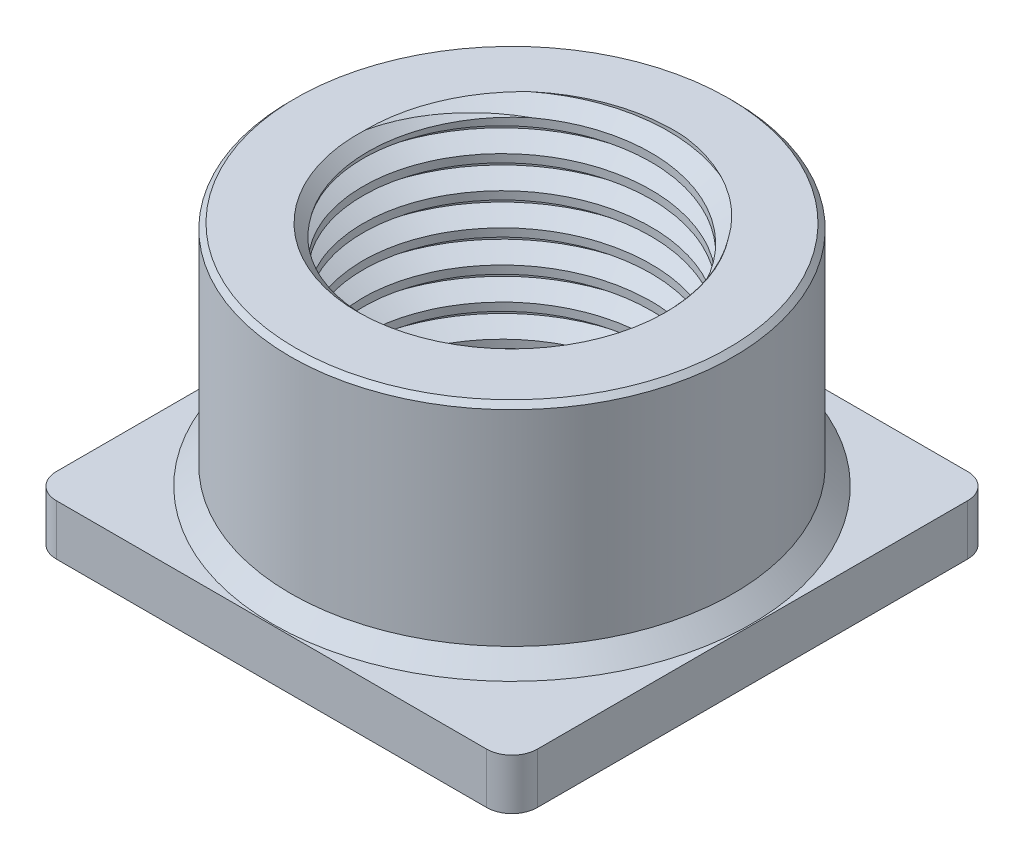
SolidWorks part; units mm, degrees
ref_plane "Front Plane" through (0, 0, 0) normal (0, 0, 1) x (1, 0, 0)
ref_plane "Top Plane" through (0, 0, 0) normal (0, 1, 0) x (1, 0, 0)
ref_plane "Right Plane" through (0, 0, 0) normal (1, 0, 0) x (0, 0, -1)
sketch "Sketch4" plane through (0, 0, 0) normal (0, 1, 0) x (1, 0, 0)
  circle A0 centre (0, 0) radius 5.69
  circle A1 centre (0, 0) radius 8.75
  dimension "D1" = 11.38
  dimension "D2" = 17.5
extrude "Boss-Extrude1" add sketch "Sketch4" along normal blind 9 separate body
sketch "Sketch7" plane through (0, 0, 0) normal (0, -1, 0) x (1, 0, 0)
  line L0 (-9.5, 9.5) -> (9.5, -9.5) construction
  line L1 (9.5, 9.5) -> (-9.5, 9.5)
  line L2 (9.5, 9.5) -> (9.5, -9.5)
  line L3 (9.5, -9.5) -> (-9.5, -9.5)
  line L4 (-9.5, 9.5) -> (-9.5, -9.5)
  circle A0 centre (0, 0) radius 6.75
  circle A1 centre (0, 0) radius 8.75 construction
  circle A2 centre (0, 0) radius 8.75 construction
  dimension "D2" = 2
  dimension "D1" = 19
extrude "Boss-Extrude2" add sketch "Sketch7" along normal blind 2
chamfer "Chamfer5" distance 1.06 angle 45 1 edges at (0, 0, -6.75)
thread "Thread1" pitch 1.27 method cut profile "Thread Profile1" start angle 0, offset 2, length 21, pitch 1.27, diameter 11.38
ref_plane "Plane1" through (-5.69, 11, 0) normal (0, 0, 1) x (-1, 0, 0)
sketch "Thread Profile1" plane through (-5.69, 11, 0) normal (0, 0, 1) x (-1, 0, 0)
  line L0 (0, 0) -> (0, 1.27) construction
  line L1 (0, 0) -> (0.6874, 0.3969)
  line L2 (0.6874, 0.3969) -> (0.6874, 0.5556)
  line L3 (0.6874, 0.5556) -> (0, 0.9525)
  line L4 (0.6874, 0.4762) -> (0, 0.4762) construction
  line L11 (0, 0) -> (0, 0.9525)
  point P2 (0, 0)
  dimension "Pitch" = 1.27
  dimension "Profile_Angle" = 60
  dimension "Profile_Land" = 0.1588
  dimension "Profile_Height" = 0.6874
sketch "Sketch5" plane through (0, 0, 0) normal (0, 1, 0) x (1, 0, 0)
  circle A0 centre (0, 0) radius 1.7544
chamfer "Chamfer3" distance 0.2 angle 45 1 edges at (0, 9, 8.75)
sketch "Sketch6" plane through (0, 0, 0) normal (0, 0, 1) x (1, 0, 0)
  line L0 (-5.69, 9) -> (5.69, 9) construction
  line L1 (0, 0) -> (0, 9) construction
  line L4 (5.0779, 9) -> (-2.5673, 9) construction
  line L5 (8.9735, 4.5) -> (-8.9735, 4.5) construction
  line L6 (5.69, 9) -> (6.09, 9)
  line L12 (6.09, 9) -> (5.69, 8.6)
  line L13 (5.69, 8.6) -> (5.69, 9)
  line L16 (5.69, 0.4) -> (5.69, 0)
  line L17 (6.09, 0) -> (5.69, 0.4)
  line L18 (5.69, 0) -> (6.09, 0)
  point P8 (0, 4.5)
  point P9 (0, 9)
  dimension "D1" = 11.38
  dimension "D2" = 0.4
revolve "Cut-Revolve1" cut sketch "Sketch6" angle 360 about L1
fillet "Fillet1" radius 1 4 edges at (-9.5, -1, -9.5) (-9.5, -1, 9.5) (9.5, -1, 9.5) (9.5, -1, -9.5)
chamfer "Chamfer4" distance 0.4 angle 45 1 edges at (0, -2, -6.75)
chamfer "Chamfer6" distance 0.7 angle 45 1 edges at (0, 0, 8.75)
